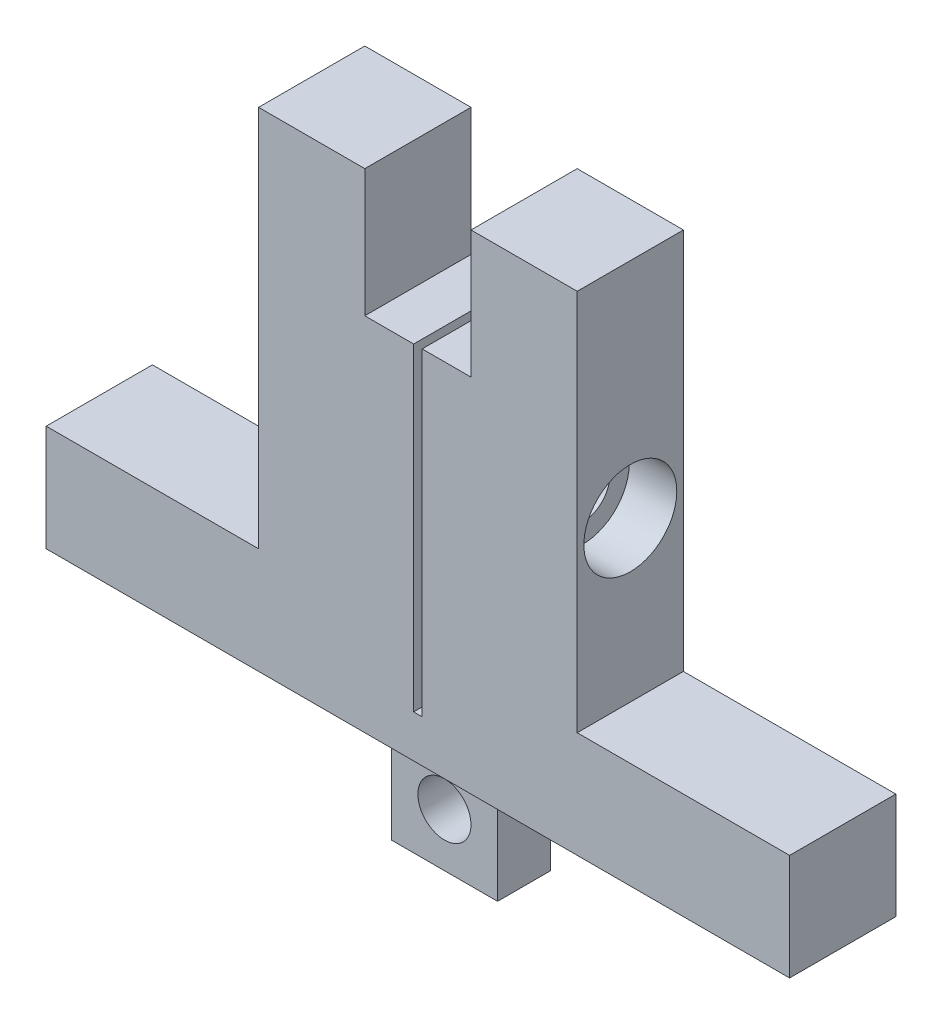
SolidWorks part; units mm, degrees
material "6061 Alloy"
ref_plane "Front Plane" through (0, 0, 0) normal (0, 0, 1) x (1, 0, 0)
ref_plane "Top Plane" through (0, 0, 0) normal (0, 1, 0) x (1, 0, 0)
ref_plane "Right Plane" through (0, 0, 0) normal (1, 0, 0) x (0, 0, -1)
sketch "Sketch2" plane through (0, 0, 0) normal (0, 0, 1) x (1, 0, 0)
  line L1 (-9.525, -15.875) -> (9.525, -15.875)
  line L2 (-9.525, -15.875) -> (-9.525, 15.875)
  line L3 (-9.525, 15.875) -> (9.525, 15.875)
  line L4 (9.525, -15.875) -> (9.525, 15.875)
  line L5 (-9.525, -15.875) -> (9.525, 15.875) construction
  line L6 (-9.525, 15.875) -> (9.525, -15.875) construction
  point P0 (0, 0)
  dimension "D1" = 31.75
  dimension "D2" = 19.05
extrude "Boss-Extrude1" add sketch "Sketch2" along normal mid plane 6.35
sketch "Sketch4" plane through (-1.5069, 3.1105, 3.175) normal (0, 0, 1) x (1, 0, 0)
  line L1 (-1.6681, 12.7645) -> (4.6819, 12.7645)
  line L2 (-1.6681, 12.7645) -> (-1.6681, 2.6045)
  line L3 (-1.6681, 2.6045) -> (4.6819, 2.6045)
  line L4 (4.6819, 12.7645) -> (4.6819, 2.6045)
  line L7 (-8.0181, 12.7645) -> (11.0319, 12.7645)
  line L8 (-8.0181, 12.7645) -> (-8.0181, 10.2245)
  line L9 (-8.0181, 10.2245) -> (11.0319, 10.2245)
  line L10 (11.0319, 12.7645) -> (11.0319, 10.2245)
  line L11 (11.0319, 12.7645) -> (-8.0181, 12.7645) construction
  line L12 (11.0319, -18.9855) -> (11.0319, 12.7645) construction
  line L13 (-8.0181, 12.7645) -> (-8.0181, -18.9855) construction
  dimension "D1" = 6.35
  dimension "D2" = 0
  dimension "D3" = 10.16
  dimension "D4" = 2.54
  dimension "D5" = 0
  dimension "D6" = 0
  dimension "D7" = 0
  dimension "D8" = 6.35
extrude "Cut-Extrude1" cut sketch "Sketch4" against normal through all contours L4 L9 | L2 L9 L4 | L9 L2 L3 L4 | L9 L2 region at (0, 14.605, 3.175) region at (-6.35, 14.605, 3.175) region at (6.35, 14.605, 3.175) region at (0, 9.525, 3.175)
sketch "Sketch20" plane through (0, 0, 3.175) normal (0, 0, 1) x (1, 0, 0)
  line L1 (9.525, -15.875) -> (22.225, -15.875)
  line L2 (9.525, -15.875) -> (9.525, -9.525)
  line L3 (9.525, -9.525) -> (22.225, -9.525)
  line L4 (22.225, -15.875) -> (22.225, -9.525)
  dimension "D1" = 12.7
  dimension "D2" = 6.35
extrude "Boss-Extrude2" add sketch "Sketch20" against normal through all
mirror "Mirror1" about plane through (0, 0, 0) normal (1, 0, 0) of "Boss-Extrude2"
sketch "Sketch21" plane through (0, 0, -3.175) normal (0, 0, -1) x (-1, 0, 0)
  line L0 (22.225, -15.875) -> (-22.225, -15.875) construction
  line L1 (-3.175, -9.525) -> (3.175, -9.525)
  line L2 (-3.175, -9.525) -> (-3.175, -22.225)
  line L3 (-3.175, -22.225) -> (3.175, -22.225)
  line L4 (3.175, -9.525) -> (3.175, -22.225)
  line L5 (-3.175, -9.525) -> (3.175, -22.225) construction
  line L6 (-3.175, -22.225) -> (3.175, -9.525) construction
  point P0 (0, -15.875)
  dimension "D1" = 6.35
  dimension "D2" = 6.35
extrude "Boss-Extrude4" add sketch "Sketch21" against normal blind 3.175 from offset 1.5875 offset against normal yes
sketch "Sketch22" plane through (0, 0, -3.175) normal (0, 0, -1) x (-1, 0, 0)
  line L0 (-3.175, -22.225) -> (3.175, -22.225) construction
  line L1 (-3.175, -15.875) -> (-3.175, -22.225) construction
  circle A0 centre (0, -19.05) radius 1.5875
  dimension "D3" = 3.175
  dimension "D1" = 3.175
  dimension "D2" = 3.175
extrude "Cut-Extrude3" cut sketch "Sketch22" against normal through all
sketch "Sketch23" plane through (0, 0, 3.175) normal (0, 0, 1) x (1, 0, 0)
  line L0 (-3.175, 5.715) -> (3.175, 5.715) construction
  line L1 (-0.254, 5.715) -> (0.254, 5.715)
  line L2 (-0.254, 5.715) -> (-0.254, -13.335)
  line L3 (-0.254, -13.335) -> (0.254, -13.335)
  line L4 (0.254, 5.715) -> (0.254, -13.335)
  line L5 (-0.254, 5.715) -> (0.254, -13.335) construction
  line L6 (-0.254, -13.335) -> (0.254, 5.715) construction
  point P0 (0, -3.81)
  dimension "D1" = 0.508
  dimension "D2" = 0
  dimension "D3" = 19.05
  dimension "D4" = 0
extrude "Cut-Extrude4" cut sketch "Sketch23" against normal through all
hole_wizard "CBORE for #4 Socket Head Cap Screw1" positions "Sketch25" profile "Sketch26" counterbore size "#4" standard "ANSI Inch" end condition up to next
sketch "Sketch25" plane through (9.525, 0, 0) normal (1, 0, 0) x (0, 0, -1)
  line L0 (-1.5875, -22.225) -> (1.5875, -22.225) construction
  point P0 (0, 0)
  dimension "D1" = 22.225
sketch "Sketch26" plane through (9.525, 0, 0) normal (0, 1, 0) x (0, 0, -1)
  line L0 (0, 0) -> (0, 9.271)
  line L1 (0, 9.271) -> (1.6319, 9.271)
  line L3 (1.6319, 9.271) -> (1.6319, 2.8448)
  line L4 (1.6319, 2.8448) -> (2.7788, 2.8448)
  line L5 (2.7788, 2.8448) -> (2.7788, 0)
  line L7 (2.7788, 0) -> (0, 0)
  line L11 (0, -6.35) -> (0, 107.95) construction
  dimension "Thru Hole Dia." = 3.2639
  dimension "Thru Hole Depth" = 9.271
  dimension "C'Bore Dia." = 5.5575
  dimension "C'Bore Depth" = 2.8448
hole_wizard "#4-40 Tapped Hole1" positions "Sketch27" profile "Sketch28" tap size "#4-40" standard "ANSI Inch" end condition through all
sketch "Sketch27" plane through (-0.254, 0, 0) normal (1, 0, 0) x (0, 0, -1)
  point P0 (0, 0)
sketch "Sketch28" plane through (-0.254, 0, 0) normal (0, 1, 0) x (0, 0, -1)
  line L0 (0, 0) -> (0, 21.971)
  line L1 (0, 21.971) -> (1.1303, 21.971)
  line L2 (1.1303, 21.971) -> (1.1303, 0)
  line L5 (1.1303, 0) -> (0, 0)
  line L11 (0, -6.35) -> (0, 107.95) construction
  dimension "Thru Tap Drill Dia." = 2.2606
  dimension "Thru Tap Drill Depth" = 21.971
cosmetic thread "Hole Thread1" parameters "D2"=2.8448
